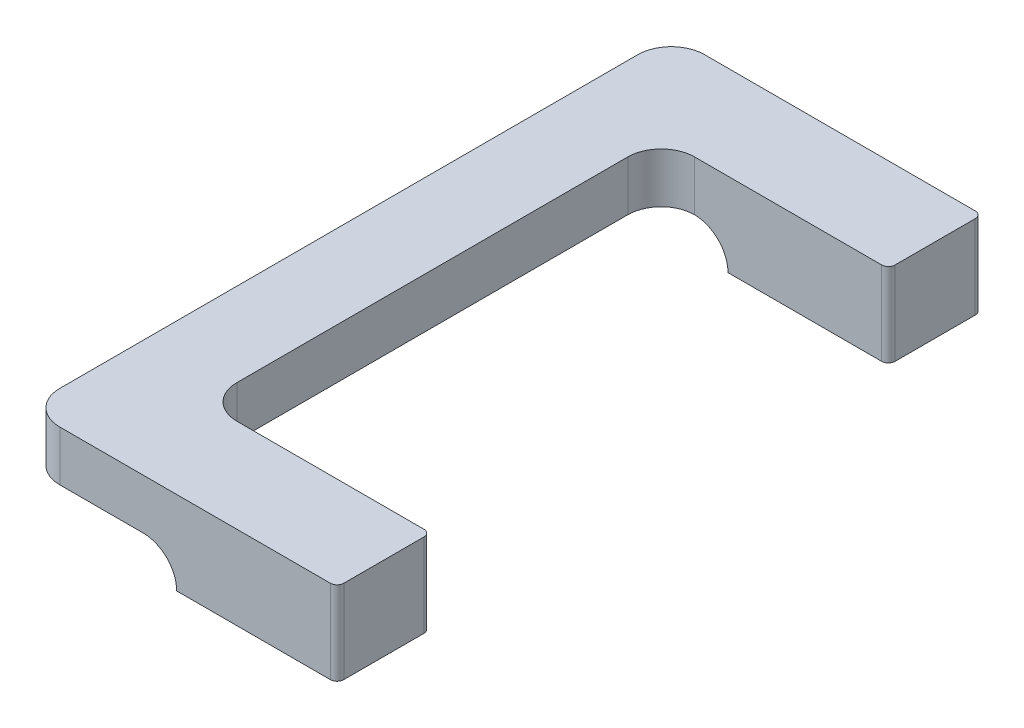
SolidWorks part; units mm, degrees
ref_plane "Front" through (0, 0, 0) normal (0, 0, 1) x (1, 0, 0)
ref_plane "Top" through (0, 0, 0) normal (0, 1, 0) x (1, 0, 0)
ref_plane "Right" through (0, 0, 0) normal (1, 0, 0) x (0, 0, -1)
sketch "Эскиз1" plane through (0, 0, 0) normal (0, 1, 0) x (1, 0, 0)
  line L0 (4.7471, 19.587) -> (-3.2529, 19.587)
  line L1 (4.7471, 19.587) -> (4.7471, 15.587)
  line L2 (4.7471, 15.587) -> (-3.2529, 15.587)
  line L3 (-3.2529, 19.587) -> (-3.2529, 15.587)
  line L4 (4.7471, -13.413) -> (-3.2529, -13.413)
  line L5 (4.7471, -13.413) -> (4.7471, -17.413)
  line L6 (4.7471, -17.413) -> (-3.2529, -17.413)
  line L7 (-3.2529, -13.413) -> (-3.2529, -17.413)
extrude "Вытянуть-Тонкостенный1" add sketch "Эскиз1" along normal blind 5 thin thin type one direction wall 0.8
sketch "Эскиз2" plane through (0, 5, 0) normal (0, 1, 0) x (1, 0, 0)
  line L0 (-4.0529, 20.387) -> (-13.0529, 20.387)
  line L1 (-13.0529, 20.387) -> (-13.0529, -18.213)
  line L2 (-13.0529, -18.213) -> (-4.0529, -18.213)
  line L3 (-4.0529, -18.213) -> (-4.0529, -12.613)
  line L4 (-4.0529, -12.613) -> (-8.0529, -12.613)
  line L5 (-8.0529, -12.613) -> (-8.0529, 14.787)
  line L6 (-8.0529, 14.787) -> (-4.0529, 14.787)
  line L7 (-4.0529, 14.787) -> (-4.0529, 20.387)
  dimension "D1" = 5
  dimension "D2" = 9
extrude "Бобышка-Вытянуть1" add sketch "Эскиз2" against normal blind 3
sketch "Эскиз3" plane through (0, 5, 0) normal (0, 1, 0) x (1, 0, 0)
  line L1 (-3.2529, 19.587) -> (4.7471, 19.587)
  line L2 (-3.2529, 19.587) -> (-3.2529, 15.587)
  line L3 (-3.2529, 15.587) -> (4.7471, 15.587)
  line L4 (4.7471, 19.587) -> (4.7471, 15.587)
  line L5 (-3.2529, -13.413) -> (4.7471, -13.413)
  line L6 (-3.2529, -13.413) -> (-3.2529, -17.413)
  line L7 (-3.2529, -17.413) -> (4.7471, -17.413)
  line L8 (4.7471, -13.413) -> (4.7471, -17.413)
extrude "Бобышка-Вытянуть2" add sketch "Эскиз3" against normal blind 1
fillet "Скругление1" radius 2 6 edges at (-4.0529, 2, -17.587) (-4.0529, 2, 15.413) (-8.0529, 3.5, 12.613) (-8.0529, 3.5, -14.787) (-13.0529, 3.5, -20.387) (-13.0529, 3.5, 18.213)
fillet "Скругление2" radius 0.4 4 edges at (5.5471, 2.5, -20.387) (5.5471, 2.5, -14.787) (5.5471, 2.5, 12.613) (5.5471, 2.5, 18.213)
